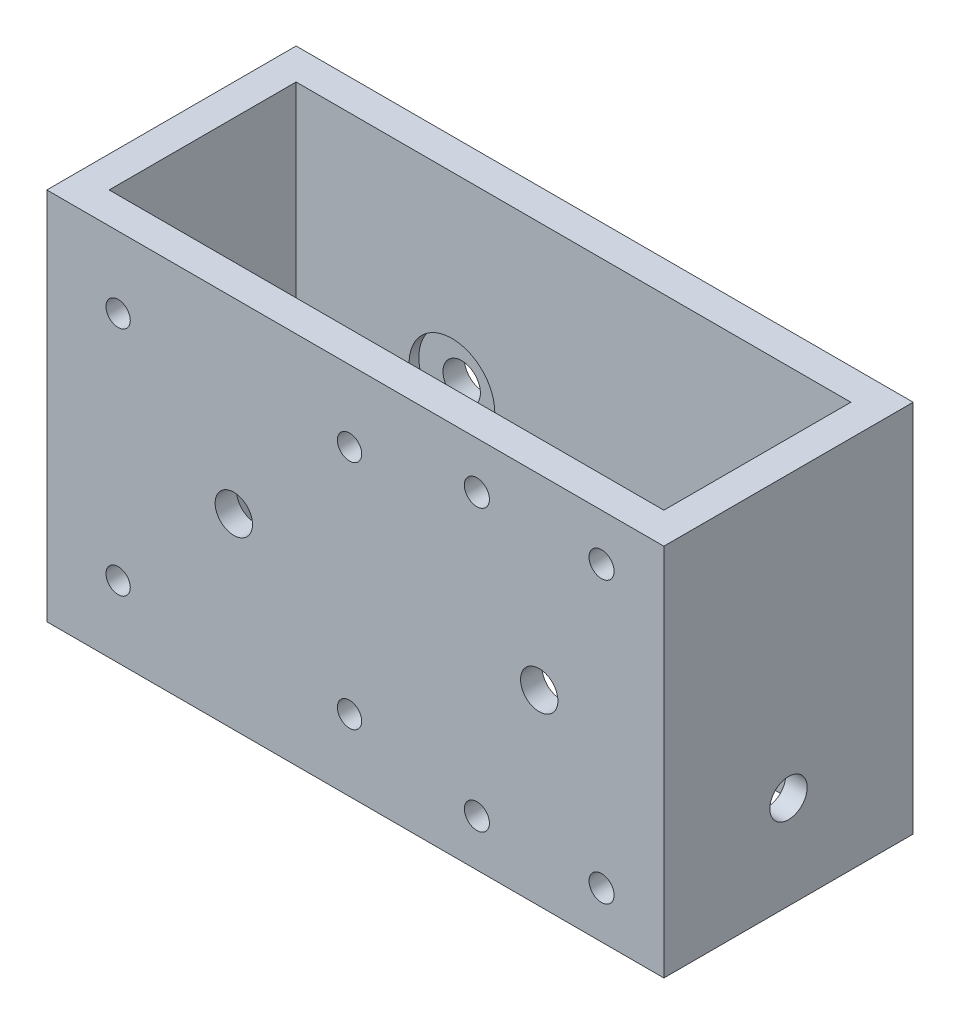
SolidWorks part; units mm, degrees
ref_plane "Front Plane" through (0, 0, 0) normal (0, 0, 1) x (1, 0, 0)
ref_plane "Top Plane" through (0, 0, 0) normal (0, 1, 0) x (1, 0, 0)
ref_plane "Right Plane" through (0, 0, 0) normal (1, 0, 0) x (0, 0, -1)
sketch "Sketch1" plane through (0, 0, 0) normal (0, 1, 0) x (1, 0, 0)
  line L1 (0, 0) -> (125.73, 0)
  line L2 (0, 0) -> (0, -50.8)
  line L3 (0, -50.8) -> (125.73, -50.8)
  line L4 (125.73, 0) -> (125.73, -50.8)
  line L5 (0, 0) -> (125.73, -50.8) construction
  line L6 (0, -50.8) -> (125.73, 0) construction
  line L7 (119.38, -44.45) -> (6.35, -44.45)
  line L8 (119.38, -44.45) -> (119.38, -6.35)
  line L9 (119.38, -6.35) -> (6.35, -6.35)
  line L10 (6.35, -44.45) -> (6.35, -6.35)
  line L11 (119.38, -44.45) -> (6.35, -6.35) construction
  line L12 (119.38, -6.35) -> (6.35, -44.45) construction
  point P4 (62.865, -25.4)
  point P6 (62.865, -25.4)
  dimension "D1" = 125.73
  dimension "D2" = 50.8
  dimension "D3" = 6.35
  dimension "D4" = 6.35
extrude "Boss-Extrude1" add sketch "Sketch1" along normal blind 76.2
sketch "Sketch2" plane through (0, 0, 50.8) normal (0, 0, 1) x (1, 0, 0)
  line L0 (0, 0) -> (125.73, 0) construction
  line L1 (8.89, 67.31) -> (67.31, 67.31) construction
  line L2 (8.89, 67.31) -> (8.89, 8.89) construction
  line L3 (8.89, 8.89) -> (67.31, 8.89) construction
  line L4 (67.31, 67.31) -> (67.31, 8.89) construction
  line L5 (8.89, 67.31) -> (67.31, 8.89) construction
  line L6 (8.89, 8.89) -> (67.31, 67.31) construction
  line L7 (0, 76.2) -> (0, 0) construction
  circle A0 centre (38.1, 38.1) radius 33.3375 construction
  circle A1 centre (14.5268, 61.6732) radius 2.4765
  circle A2 centre (61.6732, 61.6732) radius 2.4765
  circle A3 centre (61.6732, 14.5268) radius 2.4765
  circle A4 centre (14.5268, 14.5268) radius 2.4765
  circle A5 centre (38.1, 38.1) radius 3.81
  point P4 (38.1, 38.1)
  dimension "D3" = 66.675
  dimension "D4" = 4.953
  dimension "D5" = 4.953
  dimension "D6" = 4.953
  dimension "D7" = 4.953
  dimension "D8" = 7.62
  dimension "D1" = 58.42
  dimension "D2" = 58.42
  dimension "D9" = 38.1
  dimension "D10" = 38.1
extrude "Cut-Extrude1" cut sketch "Sketch2" against normal up to next contours A1 | A2 | A3 | A4
extrude "Cut-Extrude2" cut sketch "Sketch2<5>" against normal through all contours A5
sketch "Sketch2<5>" plane through (0, 0, 50.8) normal (0, 0, 1) x (1, 0, 0) same geometry as "Sketch2"
sketch "Sketch5" plane through (0, 0, 50.8) normal (0, 0, 1) x (1, 0, 0)
  line L0 (0, 0) -> (125.73, 0) construction
  line L1 (7.62, 7.62) -> (68.58, 7.62) construction
  line L2 (7.62, 7.62) -> (7.62, 68.58) construction
  line L3 (7.62, 68.58) -> (68.58, 68.58) construction
  line L4 (68.58, 7.62) -> (68.58, 68.58) construction
  line L5 (7.62, 7.62) -> (68.58, 68.58) construction
  line L6 (7.62, 68.58) -> (68.58, 7.62) construction
  circle A0 centre (100.33, 38.1) radius 3.81
  point P0 (38.1, 38.1)
  dimension "D3" = 7.62
  dimension "D5" = 31.75
  dimension "D1" = 60.96
  dimension "D2" = 60.96
  dimension "D4" = 38.1
extrude "Cut-Extrude4" cut sketch "Sketch5" against normal through all
sketch "Sketch6" plane through (0, 0, 0) normal (-1, 0, 0) x (0, 0, 1)
  line L0 (0, 38.1) -> (50.8, 38.1) construction
  line L1 (0, 76.2) -> (0, 0) construction
  line L2 (50.8, 76.2) -> (50.8, 0) construction
  line L3 (25.4, 76.2) -> (25.4, 0) construction
  line L4 (0, 76.2) -> (50.8, 76.2) construction
  line L5 (0, 0) -> (50.8, 0) construction
  circle A0 centre (25.4, 19.05) radius 3.81
  dimension "D2" = 7.62
  dimension "D1" = 19.05
extrude "Cut-Extrude5" cut sketch "Sketch6" against normal through all
sketch "Sketch7" plane through (6.35, 0, 0) normal (1, 0, 0) x (0, 0, -1)
  circle A0 centre (-25.4, 19.05) radius 8.7312
  dimension "D1" = 17.4625
extrude "Cut-Extrude6" cut sketch "Sketch7" against normal blind 1.9844
sketch "Sketch8" plane through (0, 0, 44.45) normal (0, 0, -1) x (-1, 0, 0)
  circle A0 centre (-38.1, 38.1) radius 8.7313
  circle A1 centre (-100.33, 38.1) radius 8.7313
  dimension "D1" = 17.4625
  dimension "D2" = 17.4625
extrude "Cut-Extrude7" cut sketch "Sketch8" against normal blind 1.9844
sketch "Sketch9" plane through (119.38, 0, 0) normal (-1, 0, 0) x (0, 0, 1)
  circle A0 centre (25.4, 19.05) radius 8.7312
  dimension "D1" = 17.4625
extrude "Cut-Extrude8" cut sketch "Sketch9" against normal blind 1.9844
sketch "Sketch10" plane through (0, 0, 6.35) normal (0, 0, 1) x (1, 0, 0)
  circle A0 centre (38.1, 38.1) radius 8.7312
  circle A1 centre (100.33, 38.1) radius 8.7313
  dimension "D1" = 17.4625
  dimension "D2" = 17.4625
extrude "Cut-Extrude9" cut sketch "Sketch10" against normal blind 1.9844
sketch "Sketch11" [suppressed] plane through (107.95, 0, 0) normal (-1, 0, 0) x (0, 0, 1)
  line L0 (25.4, 0) -> (25.4, 76.2) construction
  line L1 (44.45, 0) -> (6.35, 0) construction
  line L2 (44.45, 76.2) -> (6.35, 76.2) construction
  line L4 (38.1, 9.525) -> (12.7, 9.525) construction
  line L5 (38.1, 9.525) -> (38.1, 66.675) construction
  line L6 (38.1, 66.675) -> (12.7, 66.675) construction
  line L7 (12.7, 9.525) -> (12.7, 66.675) construction
  line L8 (38.1, 9.525) -> (12.7, 66.675) construction
  line L9 (38.1, 66.675) -> (12.7, 9.525) construction
  circle A0 centre (12.7, 9.525) radius 2.5527
  circle A1 centre (38.1, 9.525) radius 2.5527
  circle A2 centre (38.1, 66.675) radius 2.5527
  circle A3 centre (12.7, 66.675) radius 2.5527
  circle A4 centre (25.4, 38.1) radius 4.445
  point P6 (25.4, 38.1)
  dimension "D3" = 5.1054
  dimension "D4" = 5.1054
  dimension "D5" = 5.1054
  dimension "D6" = 5.1054
  dimension "D7" = 8.89
  dimension "D1" = 25.4
  dimension "D2" = 57.15
extrude "Cut-Extrude10" [suppressed] cut sketch "Sketch11" against normal through all
sketch "Sketch12" plane through (0, 0, 44.45) normal (0, 0, -1) x (-1, 0, 0)
  line L1 (-113.03, 66.675) -> (-87.63, 66.675) construction
  line L2 (-113.03, 66.675) -> (-113.03, 9.525) construction
  line L3 (-113.03, 9.525) -> (-87.63, 9.525) construction
  line L4 (-87.63, 66.675) -> (-87.63, 9.525) construction
  line L5 (-113.03, 66.675) -> (-87.63, 9.525) construction
  line L6 (-113.03, 9.525) -> (-87.63, 66.675) construction
  circle A0 centre (-87.63, 9.525) radius 2.5527
  circle A1 centre (-113.03, 9.525) radius 2.5527
  circle A2 centre (-113.03, 66.675) radius 2.5527
  circle A3 centre (-87.63, 66.675) radius 2.5527
  point P0 (-100.33, 38.1)
  dimension "D1" = 5.1054
  dimension "D2" = 5.1054
  dimension "D3" = 5.1054
  dimension "D4" = 5.1054
  dimension "D5" = 57.15
  dimension "D6" = 25.4
extrude "Cut-Extrude11" cut sketch "Sketch12" against normal through all
equation "\"wheelPitchD\"= 16mm"
equation "\"wheelClearanceD\"= 18mm"
equation "\"wormPitchD\"= 12mm"
equation "\"wormClearanceD\"= 14mm"
equation "\"ShaftD\"= 0.25in"
equation "\"MountingDistance\" = 14mm"
equation "\"HubDiameter\"= 12mm"
equation "\"HubWidth\"= 8mm"
equation "\"FaceWidth\"= 8mm"
